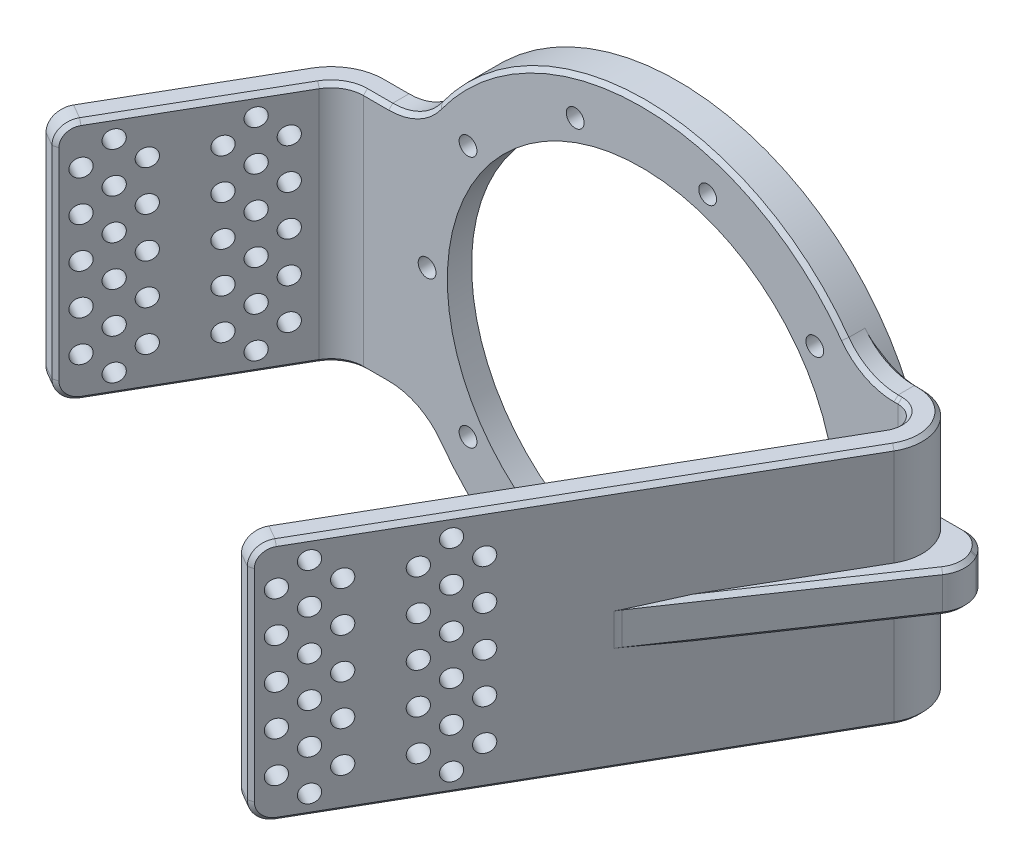
SolidWorks part; units mm, degrees
material "7075-T6 (SN)"
ref_plane "前视基准面" through (0, 0, 0) normal (0, 0, 1) x (1, 0, 0)
ref_plane "上视基准面" through (0, 0, 0) normal (0, 1, 0) x (1, 0, 0)
ref_plane "右视基准面" through (0, 0, 0) normal (1, 0, 0) x (0, 0, -1)
sketch "草图1" plane through (0, 0, 0) normal (0, 0, 1) x (1, 0, 0)
  line L1 (62, 30) -> (62, -30)
  line L2 (-62, 30) -> (-62, -30)
  line L3 (62, 30) -> (54.2586, 30)
  line L4 (62, -30) -> (54.2586, -30)
  line L5 (-54.2586, 30) -> (-62, 30)
  line L7 (-54.2586, -30) -> (-62, -30)
  arc A0 (43.6921, 30) -> (43.6921, -30) centre (0, 0) ccw construction
  arc A1 (51.9615, 30) -> (-51.9615, 30) centre (0, 0) ccw construction
  circle A2 centre (0, 0) radius 48
  arc A3 (54.2586, 30) -> (-54.2586, 30) centre (0, 0) ccw
  circle A4 centre (0, 0) radius 53 construction
  circle A5 centre (0, 0) radius 60 construction
  circle A6 centre (0, 0) radius 62 construction
  arc A8 (-54.2586, -30) -> (54.2586, -30) centre (0, 0) ccw
  point P12 (62, 0)
  point P15 (-62, 0)
  dimension "D1" = 5
  dimension "D2" = 2
extrude "凸台-拉伸1" add sketch "草图1" along normal blind 6
sketch "草图2" plane through (0, -30, 0) normal (0, -1, 0) x (1, 0, 0)
  line L0 (-99.738, 51.6754) -> (-73.3673, 6)
  line L1 (-104.9342, 48.6754) -> (-76.8314, 0)
  line L2 (-62, 0) -> (-54.2586, 0) construction
  line L3 (-62, 6) -> (-54.2586, 6) construction
  line L4 (-76.8314, 0) -> (-62, 0)
  line L5 (-73.3673, 6) -> (-62, 6)
  line L6 (9.3812, 114.6754) -> (72.125, 6)
  line L7 (14.5773, 117.6754) -> (82.5173, 0)
  line L8 (-104.9342, 48.6754) -> (-81.0842, 7.366) construction
  line L9 (-99.738, 51.6754) -> (-75.888, 10.366) construction
  line L10 (9.3812, 114.6754) -> (33.2312, 73.366) construction
  line L11 (14.5773, 117.6754) -> (38.4273, 76.366) construction
  line L12 (-104.9342, 48.6754) -> (-99.738, 51.6754)
  line L13 (9.3812, 114.6754) -> (14.5773, 117.6754)
  line L14 (-62, 0) -> (-62, 6)
  line L15 (62, 6) -> (62, 0)
  line L16 (62, 6) -> (72.125, 6)
  line L17 (62, 0) -> (82.5173, 0)
  dimension "D1" = 6
  dimension "D2" = 6
extrude "凸台-拉伸2" add sketch "草图2" against normal up to surface (60 mm away) up to face at (-58.1293, 30, 3)
fillet "圆角3" radius 8 1 edges at (-73.3673, 0, 6)
fillet "圆角4" radius 14 1 edges at (-76.8314, 0, 0)
fillet "圆角6" radius 5 4 edges at (11.9793, -30, 116.1754) (11.9793, 30, 116.1754) (-102.3361, 30, 50.1754) (-102.3361, -30, 50.1754)
fillet "圆角7" radius 5 1 edges at (72.125, 0, 6)
fillet "圆角8" radius 11 1 edges at (82.5173, 0, 0)
fillet "圆角9" radius 15 4 edges at (-54.2586, -30, 3) (-54.2586, 30, 3) (54.2586, 30, 3) (54.2586, -30, 3)
sketch "草图3" plane through (61.888, 0, 35.731) normal (0.866, 0, 0.5) x (0.5, 0, -0.866)
  line L1 (-51.9212, 20) -> (-51.9212, -20) construction
  circle A0 centre (-89.6212, 0) radius 2.2
  circle A1 centre (-89.6212, 10) radius 2.2
  circle A2 centre (-89.6212, 20) radius 2.2
  circle A3 centre (-89.6212, -10) radius 2.2
  circle A4 centre (-89.6212, -20) radius 2.2
  circle A5 centre (-83.6212, 5) radius 2.2
  circle A6 centre (-83.6212, 15) radius 2.2
  circle A7 centre (-83.6212, 25) radius 2.2
  circle A8 centre (-83.6212, -5) radius 2.2
  circle A9 centre (-83.6212, -15) radius 2.2
  circle A10 centre (-83.6212, -25) radius 2.2
  circle A11 centre (-77.6212, -20) radius 2.2
  circle A12 centre (-77.6212, -10) radius 2.2
  circle A13 centre (-77.6212, 0) radius 2.2
  circle A14 centre (-77.6212, 10) radius 2.2
  circle A15 centre (-77.6212, 20) radius 2.2
  circle A16 centre (-63.9212, 0) radius 2.2
  circle A17 centre (-63.9212, 10) radius 2.2
  circle A18 centre (-63.9212, 20) radius 2.2
  circle A19 centre (-63.9212, -10) radius 2.2
  circle A20 centre (-63.9212, -20) radius 2.2
  circle A21 centre (-57.9212, -25) radius 2.2
  circle A22 centre (-57.9212, -15) radius 2.2
  circle A24 centre (-57.9212, -5) radius 2.2
  circle A25 centre (-57.9212, 5) radius 2.2
  circle A26 centre (-57.9212, 15) radius 2.2
  circle A27 centre (-57.9212, 25) radius 2.2
  circle A28 centre (-51.9212, 20) radius 2.2
  circle A29 centre (-51.9212, 10) radius 2.2
  circle A30 centre (-51.9212, 0) radius 2.2
  circle A31 centre (-51.9212, -10) radius 2.2
  circle A32 centre (-51.9212, -20) radius 2.2
extrude "切除-拉伸1" cut sketch "草图3" against normal through all both and the other way through all
sketch "草图6" plane through (0, 0, 0) normal (0, 0, -1) x (-1, 0, 0)
  circle A0 centre (0, 0) radius 60
  circle A1 centre (0, 0) radius 62
extrude "凸台-拉伸3" add sketch "草图6" along normal blind 3
chamfer "倒角3" distance 1 angle 45 1 edges at (-60, 0, -3)
sketch "草图7" plane through (0, 0, -3) normal (0, 0, -1) x (-1, 0, 0)
  circle A0 centre (0, 0) radius 53 construction
  circle A1 centre (-53, 0) radius 2.2
  circle A2 centre (-42.8779, 31.1526) radius 2.2
  circle A3 centre (-16.3779, 50.406) radius 2.2
  circle A4 centre (16.3779, 50.406) radius 2.2
  circle A5 centre (42.8779, 31.1526) radius 2.2
  circle A6 centre (53, 0) radius 2.2
  circle A7 centre (42.8779, -31.1526) radius 2.2
  circle A8 centre (16.3779, -50.406) radius 2.2
  circle A9 centre (-16.3779, -50.406) radius 2.2
  circle A10 centre (-42.8779, -31.1526) radius 2.2
  point P26 (0, 0)
  dimension "D1" = 10
extrude "切除-拉伸3" cut sketch "草图7" against normal blind 11
chamfer "倒角4" distance 1 angle 45 46 edges at (-55.6444, -31.6491, 0) (-65.6152, -30, 0) (-75.7485, -30, 1.8756) (-91.6535, -30, 25.6727) (-104.2019, -28.5355, 47.4072) (-104.9342, 0, 48.6754) (-104.2019, 28.5355, 47.4072) (-91.6535, 30, 25.6727) (-55.6444, 31.6491, 0) (-75.7485, 30, 1.8756) (-65.6152, 30, 0) (-72.7485, -30, 7.0718) (-86.4573, -30, 28.6727) (-65.6152, -30, 6) (-99.0058, -28.5355, 50.4072) (-55.6444, -31.6491, 6) (-99.738, 0, 51.6754) (0, -62, 6) (-99.0058, 28.5355, 50.4072) (55.6444, -31.6491, 6) (-86.4573, 30, 28.6727) (62.9734, -30, 6) (-72.7485, 30, 7.0718) (67.7949, -30, 8.5) (-65.6152, 30, 6) (39.838, -30, 61.9227) (-55.6444, 31.6491, 6) (10.1134, -28.5355, 113.4072) (0, 62, 6) (9.3812, 0, 114.6754) (55.6444, 31.6491, 6) (10.1134, 28.5355, 113.4072) (62.9734, 30, 6) (39.838, 30, 61.9227) (67.7949, 30, 8.5) (45.0342, -30, 64.9227) (55.6444, -31.6491, 0) (62.9734, -30, 0) (72.991, -30, 5.5) (15.3096, -28.5355, 116.4072) (14.5773, 0, 117.6754) (15.3096, 28.5355, 116.4072) (55.6444, 31.6491, 0) (45.0342, 30, 64.9227) (62.9734, 30, 0) (72.991, 30, 5.5)
sketch "草图8" plane through (0, 0, 0) normal (0, 1, 0) x (1, 0, 0)
  line L0 (63.4647, 0) -> (78.4647, 0)
  line L2 (72.991, -16.5) -> (47.991, -59.8013)
  line L4 (78.4647, 0) -> (83.1358, -8.0905)
  line L5 (72.991, -16.5) -> (17.0773, -113.3453) construction
  line L7 (47.991, -59.8013) -> (83.1358, -8.0905)
  arc A0 (72.991, -16.5) -> (63.4647, 0) centre (63.4647, -11) ccw construction
  arc A1 (72.991, -16.5) -> (63.4647, 0) centre (63.4647, -11) ccw
extrude "凸台-拉伸5" add sketch "草图8" along normal mid plane 10
fillet "圆角17" radius 20 1 edges at (47.991, 0, 59.8013)
fillet "圆角19" radius 7.5 2 edges at (83.1358, 0, 8.0905) (78.4647, 0, 0)
chamfer "倒角7" distance 1 angle 45 12 edges at (48.0024, -5, 59.8084) (64.4473, -5, 35.5881) (81.7831, -5, 8.0408) (80.7066, -5, 3.883) (77.8846, -5, 1.0048) (68.7997, -5, 0) (48.0024, 5, 59.8084) (64.4473, 5, 35.5881) (81.7831, 5, 8.0408) (80.7066, 5, 3.883) (77.8846, 5, 1.0048) (68.7997, 5, 0)
